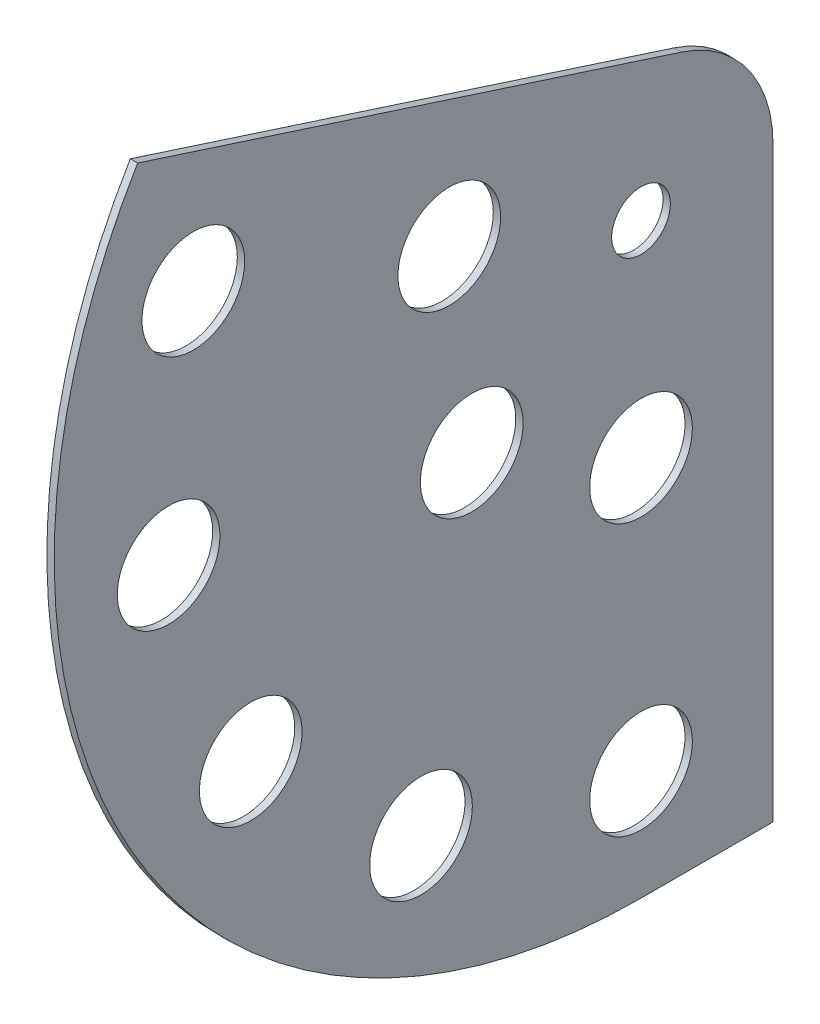
SolidWorks part; units mm, degrees
ref_plane "Front Plane" through (0, 0, 0) normal (0, 0, 1) x (1, 0, 0)
ref_plane "Top Plane" through (0, 0, 0) normal (0, 1, 0) x (1, 0, 0)
ref_plane "Right Plane" through (0, 0, 0) normal (1, 0, 0) x (0, 0, -1)
sketch "Sketch1" plane through (0, 0, 0) normal (1, 0, 0) x (0, 0, -1)
  line L0 (-217.8994, 130.5215) -> (17.5832, 54.3779)
  line L4 (57.15, 0) -> (57.15, -254)
  line L5 (57.15, -254) -> (0, -254)
  arc A0 (-217.8994, 130.5215) -> (0, -254) centre (0, 0) ccw
  circle A1 centre (0, 0) radius 12.7
  arc A2 (57.15, 0) -> (17.5832, 54.3779) centre (0, 0) ccw
  circle A3 centre (0, 0) radius 57.15 construction
  circle A4 centre (0, -88.9) radius 22.225
  circle A5 centre (-73.2648, -50.3535) radius 22.225
  circle A6 centre (-82.9953, 31.8589) radius 22.225
  circle A7 centre (0, -206.2305) radius 22.225
  circle A8 centre (-95.2266, -182.9287) radius 22.225
  circle A9 centre (-168.9341, -118.2889) radius 22.225
  circle A10 centre (-204.4661, -26.9185) radius 22.225
  circle A11 centre (-193.7932, 70.535) radius 22.225
  point P18 (0, 0)
  point P29 (0, 0)
  dimension "D1" = 25.4
  dimension "D2" = 254
  dimension "D3" = 3
  dimension "D4" = 44.45
  dimension "D6" = 5
  dimension "D5" = 88.9
extrude "Boss-Extrude1" add sketch "Sketch1" along normal blind 3.175
